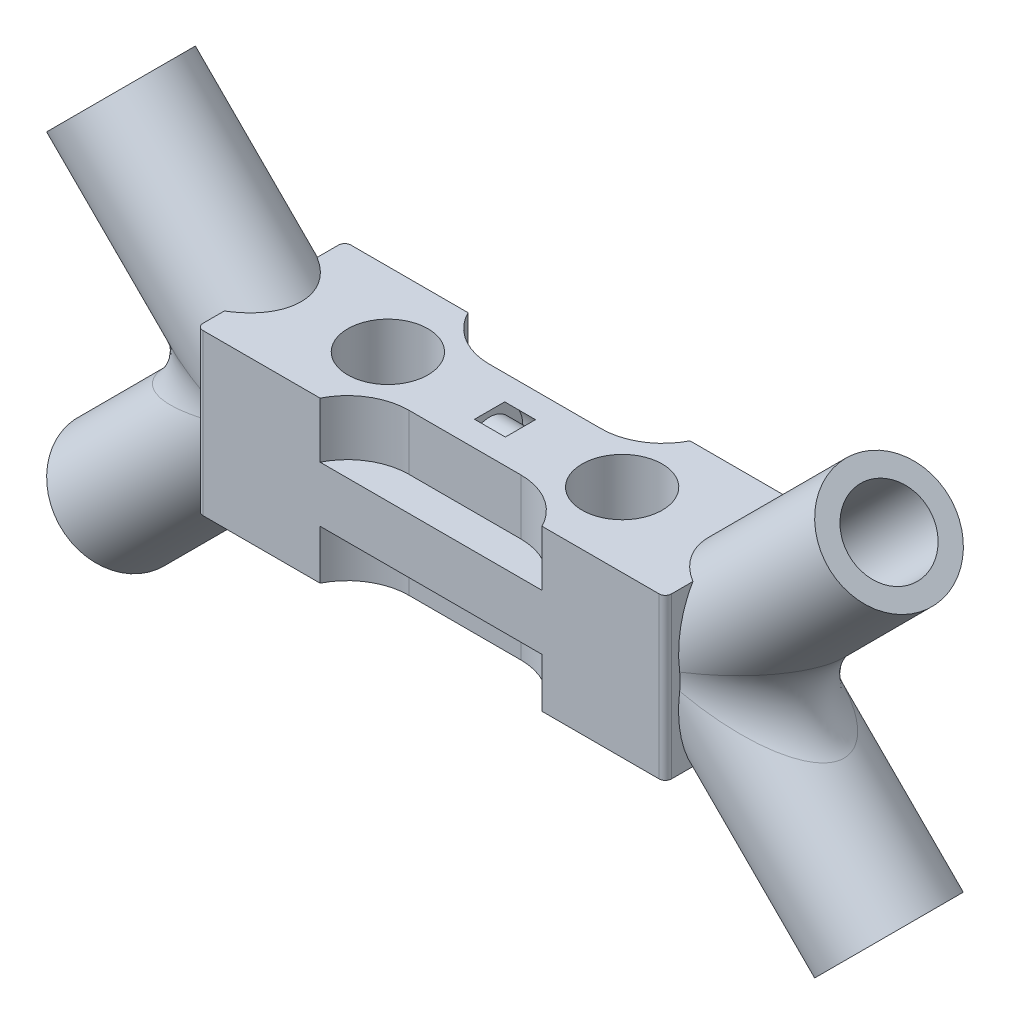
SolidWorks part; units mm, degrees
ref_plane "Alzado" through (0, 0, 0) normal (0, 0, 1) x (1, 0, 0)
ref_plane "Planta" through (0, 0, 0) normal (0, 1, 0) x (1, 0, 0)
ref_plane "Vista lateral" through (0, 0, 0) normal (1, 0, 0) x (0, 0, -1)
sketch "Croquis1" plane through (0, 0, 0) normal (0, 1, 0) x (1, 0, 0)
  line L0 (0, 0) -> (-38, 0) construction
  line L1 (-18, 6.5) -> (18, 6.5)
  line L3 (-18, -6.5) -> (18, -6.5)
  line L5 (-18, 6.5) -> (18, -6.5) construction
  line L6 (-18, -6.5) -> (18, 6.5) construction
  line L7 (-38, -12) -> (-38, 12)
  line L10 (0, 0) -> (0, -6.5) construction
  line L12 (38, -12) -> (38, 12)
  line L14 (-38, 12) -> (-18, 12)
  line L15 (-18, 12) -> (-18, 6.5)
  line L16 (-38, -12) -> (-18, -12)
  line L17 (-18, -12) -> (-18, -6.5)
  line L18 (38, 12) -> (18, 12)
  line L19 (18, 12) -> (18, 6.5)
  line L20 (38, -12) -> (18, -12)
  line L21 (18, -12) -> (18, -6.5)
  point P4 (0, 0)
  point P14 (-38, 0)
  point P16 (0, 6.5)
  dimension "D1" = 20
  dimension "D4" = 24
  dimension "D2" = 36
  dimension "D3" = 13
extrude "Saliente-Extruir2" add sketch "Croquis1" along normal mid plane 26
fillet "Redondeo8" radius 10 4 edges at (18, 0, -6.5) (18, 0, 6.5) (-18, 0, -6.5) (-18, 0, 6.5)
sketch "Croquis2" plane through (0, 0, 0) normal (0, 1, 0) x (1, 0, 0)
  line L0 (-38, -5) -> (-52.1421, -19.1421)
  line L2 (-38, -5) -> (-38, 5)
  line L3 (38, -5) -> (38, 5)
  line L4 (38, -12) -> (38, 12) construction
  line L5 (38, -5) -> (52.1421, -19.1421)
  line L6 (38, 5) -> (52.1421, 19.1421)
  line L7 (0, 0) -> (0, -6.5) construction
  line L8 (-9.0697, -6.5) -> (9.0697, -6.5) construction
  line L9 (-38, 5) -> (-52.1421, 19.1421)
  point P15 (38, 0)
  dimension "D2" = 10
  dimension "D5" = 45
  dimension "D6" = 45
  dimension "D7" = 20
ref_plane "Plano1" through (52.1421, 0, 0) normal (1, 0, 0) x (0, 0, -1)
sketch "Croquis22" plane through (0, 0, 0) normal (0, 0, 1) x (1, 0, 0)
  line L0 (-62.2843, 28.2843) -> (-34, 0)
  line L1 (-34, 0) -> (-55.2132, -21.2132)
  line L2 (-34, 0) -> (-38, 0) construction
  line L3 (-38, 13) -> (-38, -13) construction
  line L4 (32, 0) -> (55.2132, -21.2132)
  line L5 (62.2843, 28.2843) -> (32, 0)
  line L6 (0, 0) -> (0, -13) construction
  line L7 (-9.0697, -13) -> (9.0697, -13) construction
  dimension "D6" = 45
  dimension "D2" = 45
  dimension "D3" = 40
  dimension "D4" = 4
  dimension "D5" = 30
ref_plane "Plano2" through (-62.2843, 28.2843, 0) normal (0.7071, -0.7071, 0) x (-0.7071, -0.7071, 0)
sketch "Croquis33" plane through (-62.2843, 28.2843, 0) normal (0.7071, -0.7071, 0) x (-0.7071, -0.7071, 0)
  circle A0 centre (0, 0) radius 9.85
  dimension "D1" = 19.7
ref_plane "Plano3" through (62.2843, 28.2843, 0) normal (-0.7308, -0.6826, 0) x (0, 0, 1)
sketch "Croquis35" plane through (0, 0, 0) normal (0, 1, 0) x (1, 0, 0)
  line L0 (-19, 0) -> (19, 0) construction
  circle A0 centre (-19, 0) radius 6.5
  circle A1 centre (19, 0) radius 6.5
  point P4 (0, 0)
  dimension "D1" = 13
  dimension "D2" = 38
extrude "Cortar-Extruir1" cut sketch "Croquis35" against normal mid plane 30 contours A1 | A0
extrude "Saliente-Extruir3" add sketch "Croquis33" along normal up to body separate body
sketch "Croquis44" plane through (-45.2843, 45.2843, 0) normal (-0.7071, 0.7071, 0) x (0, 0, 1)
  circle A0 centre (0, -24.0416) radius 6.5
  dimension "D1" = 13
extrude "Cortar-Extruir8" cut sketch "Croquis44" against normal blind 28
mirror "Simetría4" about plane through (0, 0, 0) normal (1, 0, 0) of "Cortar-Extruir8", "Saliente-Extruir3"
mirror "Simetría5" about plane through (0, 0, 0) normal (0, 1, 0) of "Simetría4"
ref_plane "Plano4" through (-55.2132, -21.2132, 0) normal (-0.7071, -0.7071, 0) x (0, 0, 1)
ref_plane "Plano5" through (55.2132, -21.2132, 0) normal (0.7382, -0.6746, 0) x (0, 0, -1)
fillet "Redondeo4" radius 1 4 edges at (-38, 0, 12) (38, 0, 12) (-38, 0, -12) (38, 0, -12)
fillet "Redondeo9" radius 10 2 edges at (-47.93, 0, 0) (47.93, 0, 0)
sketch "Croquis45" plane through (0, 0, 12) normal (0, 0, 1) x (1, 0, 0)
  line L0 (-18, 13) -> (-18, -13) construction
  line L1 (-18, 4) -> (18, 4)
  line L2 (-18, 4) -> (-18, -5)
  line L3 (-18, -5) -> (18, -5)
  line L4 (18, 4) -> (18, -5)
  line L5 (18, 13) -> (18, -13) construction
  line L6 (-9.0697, 13) -> (9.0697, 13) construction
  dimension "D1" = 9
  dimension "D2" = 9
extrude "Saliente-Extruir4" add sketch "Croquis45" against normal up to next
mirror "Simetría7" about plane through (0, 0, 0) normal (0, 0, 1) of "Saliente-Extruir4"
sketch "Croquis47" plane through (0, 0, 0) normal (0, 0, 1) x (1, 0, 0)
  line L0 (-51.7837, 31.7137) -> (-48.2482, 28.1782)
  line L1 (-33.07, 13) -> (-55.3193, 35.2493) construction
  line L2 (-48.2482, 28.1782) -> (-48.9553, 27.4711)
  line L3 (-48.9553, 27.4711) -> (-52.4908, 31.0066)
  line L4 (-52.4908, 31.0066) -> (-51.7837, 31.7137)
  line L5 (-55.3193, 35.2493) -> (-69.2493, 21.3193) construction
  line L6 (-62.2843, 28.2843) -> (0, -27) construction
  line L7 (-57.6881, 32.8805) -> (-66.8805, 23.6881) construction
  dimension "D1" = 1
  dimension "D2" = 5
  dimension "D3" = 5
revolve "Cortar-Revolución1" cut sketch "Croquis47" angle 360 about L6 rebuild error yes
sketch "Croquis49" plane through (0, 0, 0) normal (0, 0, 1) x (1, 0, 0)
  line L0 (-48.2482, -28.1782) -> (-48.9553, -27.4711)
  line L1 (-55.3193, -35.2493) -> (-33.07, -13) construction
  line L2 (-48.9553, -27.4711) -> (-52.4908, -31.0066)
  line L3 (-52.4908, -31.0066) -> (-51.7837, -31.7137)
  line L4 (-51.7837, -31.7137) -> (-48.2482, -28.1782)
  line L5 (-69.2493, -21.3193) -> (-55.3193, -35.2493) construction
  line L6 (-62.2843, -28.2843) -> (-5.3962, 21.6038) construction
  point P8 (-50.016, -29.946)
  dimension "D1" = 5
  dimension "D2" = 5
  dimension "D3" = 1
revolve "Cortar-Revolución2" cut sketch "Croquis49" angle 360 about L6 rebuild error yes
mirror "Simetría12" about plane through (0, 0, 0) normal (1, 0, 0) rebuild error yes
sketch "Croquis50" plane through (0, 0, 0) normal (1, 0, 0) x (0, 0, -1)
  line L0 (0, -8.2) -> (0, 8.2) construction
  line L1 (-5.3881, -8.2) -> (-5.3881, 8.2)
  line L2 (5.3881, -8.2) -> (5.3881, 8.2)
  line L3 (-7.5181, -13) -> (7.5181, -13) construction
  line L4 (7.5181, 13) -> (-7.5181, 13) construction
  line L5 (0, -8.2) -> (0, 8.2) construction
  line L6 (-3.8881, -8.2) -> (-3.8881, 8.2)
  line L7 (3.8881, -8.2) -> (3.8881, 8.2)
  line L8 (-12, -13) -> (-12, 13) construction
  arc A0 (-5.3881, -8.2) -> (5.3881, -8.2) centre (0, -8.2) ccw
  arc A1 (5.3881, 8.2) -> (-5.3881, 8.2) centre (0, 8.2) ccw
  arc A2 (-3.8881, -8.2) -> (3.8881, -8.2) centre (0, -8.2) ccw
  arc A3 (3.8881, 8.2) -> (-3.8881, 8.2) centre (0, 8.2) ccw
  point P3 (0, 0)
  point P14 (0, 0)
  point P21 (-12, 0)
  dimension "D1" = 4.8
  dimension "D2" = 4.8
  dimension "D3" = 1.5
  dimension "D4" = 6.6119
extrude "Cortar-Extruir10" cut sketch "Croquis50" against normal mid plane 5
